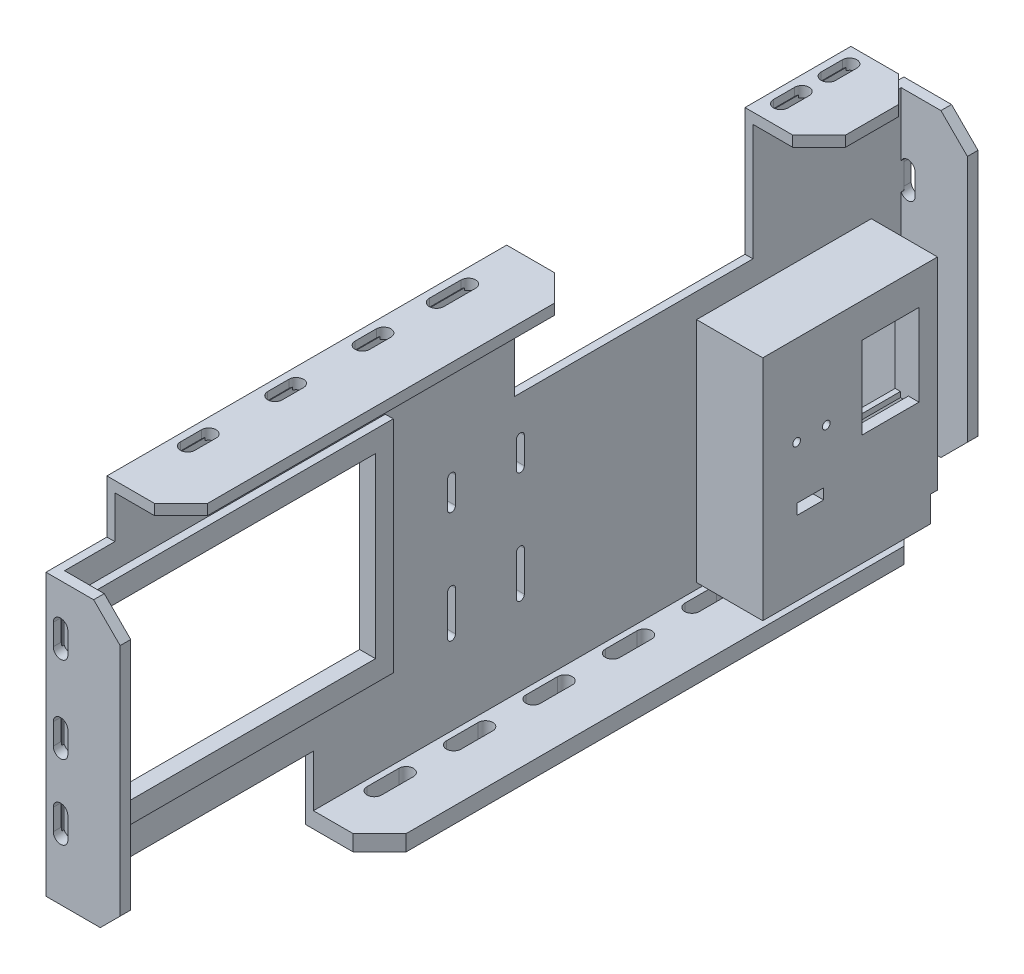
SolidWorks part; units mm, degrees
ref_plane "前视基准面" through (0, 0, 0) normal (0, 0, 1) x (1, 0, 0)
ref_plane "上视基准面" through (0, 0, 0) normal (0, 1, 0) x (1, 0, 0)
ref_plane "右视基准面" through (0, 0, 0) normal (1, 0, 0) x (0, 0, -1)
other "Configuration Table"
sketch "草图1" plane through (0, 0, 0) normal (1, 0, 0) x (0, 0, -1)
  line L0 (10, 87) -> (70, 87)
  line L1 (0, 0) -> (80, 0)
  line L2 (0, 0) -> (0, 97)
  line L3 (0, 97) -> (80, 97)
  line L4 (80, 0) -> (80, 97)
  line L5 (70, 10) -> (70, 87)
  line L6 (10, 10) -> (70, 10)
  line L7 (10, 10) -> (10, 87)
  dimension "D1" = 97
  dimension "D2" = 80
  dimension "D3" = 10
extrude "凸台-拉伸1" add sketch "草图1" along normal blind 6
sketch "草图2" plane through (6, 0, 0) normal (1, 0, 0) x (0, 0, -1)
  line L0 (80, 97) -> (0, 97) construction
  line L1 (10, 87) -> (70, 87)
  line L2 (10, 87) -> (10, 97)
  line L3 (10, 97) -> (70, 97)
  line L4 (70, 87) -> (70, 97)
  line L5 (0, 0) -> (80, 0) construction
  line L6 (10, 10) -> (70, 10)
  line L7 (10, 10) -> (10, 0)
  line L8 (10, 0) -> (70, 0)
  line L9 (70, 10) -> (70, 0)
extrude "凸台-拉伸2" add sketch "草图2" along normal blind 25
sketch "草图3" plane through (31, 0, 0) normal (1, 0, 0) x (0, 0, -1)
  line L1 (10, 87) -> (70, 87)
  line L2 (10, 87) -> (10, 10)
  line L3 (10, 10) -> (70, 10)
  line L4 (70, 87) -> (70, 10)
extrude "凸台-拉伸3" add sketch "草图3" against normal blind 4
sketch "草图4" plane through (27, 0, 0) normal (-1, 0, 0) x (0, 0, 1)
  line L0 (-70, 10) -> (-70, 87) construction
  line L1 (-66, 46) -> (-44.5, 46)
  line L2 (-66, 46) -> (-66, 77)
  line L3 (-66, 77) -> (-44.5, 77)
  line L4 (-44.5, 46) -> (-44.5, 77)
  line L5 (-70, 87) -> (-10, 87) construction
  dimension "D1" = 4
  dimension "D2" = 21.5
  dimension "D3" = 31
  dimension "D4" = 10
extrude "切除-拉伸1" cut sketch "草图4" against normal blind 4
sketch "草图5" plane through (27, 0, 0) normal (-1, 0, 0) x (0, 0, 1)
  line L0 (-66, 46) -> (-44.5, 46) construction
  line L1 (-44.5, 46) -> (-44.5, 77) construction
  line L2 (-66, 77) -> (-66, 46) construction
  line L3 (-44.5, 77) -> (-66, 77) construction
  line L4 (-66, 46) -> (-44.5, 46)
  line L5 (-44.5, 46) -> (-44.5, 77)
  line L6 (-66, 77) -> (-66, 46)
  line L7 (-44.5, 77) -> (-66, 77)
  line L8 (-68, 44) -> (-42.5, 44)
  line L9 (-42.5, 44) -> (-42.5, 79)
  line L10 (-42.5, 79) -> (-68, 79)
  line L11 (-68, 79) -> (-68, 44)
  dimension "D1" = 2
extrude "凸台-拉伸4" add sketch "草图5" along normal blind 5
sketch "草图6" plane through (0, 44, 0) normal (0, -1, 0) x (1, 0, 0)
  line L0 (22, -68) -> (27, -68) construction
  line L1 (24, -44.5) -> (27, -44.5)
  line L2 (24, -44.5) -> (24, -66)
  line L3 (24, -66) -> (27, -66)
  line L4 (27, -44.5) -> (27, -66)
  line L5 (22, -42.5) -> (27, -42.5) construction
  line L6 (22, -68) -> (22, -42.5) construction
  dimension "D1" = 2
  dimension "D2" = 2
  dimension "D3" = 2
  dimension "D4" = 3
extrude "切除-拉伸2" cut sketch "草图6" against normal blind 37
sketch "草图7" plane through (27, 0, 0) normal (-1, 0, 0) x (0, 0, 1)
  line L0 (-42.5, 44) -> (-42.5, 79) construction
  line L1 (-34.5, 44) -> (-16.3, 44)
  line L2 (-34.5, 44) -> (-34.5, 74.1)
  line L3 (-34.5, 74.1) -> (-16.3, 74.1)
  line L4 (-16.3, 44) -> (-16.3, 74.1)
  dimension "D1" = 18.2
  dimension "D2" = 30.1
  dimension "D3" = 8
  dimension "D4" = 44
extrude "切除-拉伸3" cut sketch "草图7" against normal blind 1.5
sketch "草图8" plane through (28.5, 0, 0) normal (-1, 0, 0) x (0, 0, 1)
  line L0 (-34.5, 44) -> (-16.3, 44) construction
  line L1 (-34.5, 44) -> (-16.3, 44) construction
  line L2 (-34.5, 74.1) -> (-34.5, 44) construction
  line L3 (-16.3, 44) -> (-16.3, 74.1) construction
  circle A0 centre (-31, 56) radius 1.45
  circle A1 centre (-19.8, 56) radius 1.45
  dimension "D1" = 12
  dimension "D3" = 2.9
  dimension "D4" = 2.9
  dimension "D2" = 12
  dimension "D5" = 3.5
  dimension "D6" = 3.5
extrude "切除-拉伸5" cut sketch "草图8" against normal blind 4.5
fillet "圆角1" radius 3 1 edges at (0, 0, -40)
fillet "圆角2" radius 3 1 edges at (0, 97, -40)
sketch "草图9" plane through (0, 97, 0) normal (0, 1, 0) x (1, 0, 0)
  line L0 (0, 0) -> (0, 80) construction
  line L1 (31, 70) -> (6, 70) construction
  circle A0 centre (6.2, 54) radius 2.75
  circle A1 centre (6.2, 46) radius 2.75
  circle A2 centre (6.2, 36) radius 2.75
  circle A3 centre (6.2, 28) radius 2.75
  dimension "D1" = 6.2
  dimension "D3" = 5.5
  dimension "D2" = 16
  dimension "D4" = 8
  dimension "D5" = 10
  dimension "D6" = 8
extrude "切除-拉伸6" cut sketch "草图9" against normal blind 10
sketch "草图10" plane through (0, 0, 0) normal (-1, 0, 0) x (0, 0, 1)
  line L1 (-70, 87) -> (-10, 87)
  line L2 (-70, 87) -> (-70, 92)
  line L3 (-70, 92) -> (-10, 92)
  line L4 (-10, 87) -> (-10, 92)
  dimension "D1" = 5
extrude "切除-拉伸7" cut sketch "草图10" against normal blind 20
sketch "草图11" plane through (0, 0, 0) normal (-1, 0, 0) x (0, 0, 1)
  line L0 (-10, 92) -> (-10, 10) construction
  line L1 (-70, 10) -> (-10, 10)
  line L2 (-70, 10) -> (-70, 20)
  line L3 (-70, 20) -> (-10, 20)
  line L4 (-10, 10) -> (-10, 20)
  dimension "D1" = 10
extrude "凸台-拉伸5" add sketch "草图11" against normal blind 5
sketch "草图12" plane through (0, 0, 0) normal (-1, 0, 0) x (0, 0, 1)
  line L0 (0, 0) -> (-80, 0) construction
  line L1 (0, 94) -> (0, 3) construction
  circle A0 centre (-61, 14) radius 2.7
  circle A1 centre (-46, 14) radius 2.7
  circle A2 centre (-30, 14) radius 2.7
  circle A3 centre (-15, 14) radius 2.7
  dimension "D1" = 14
  dimension "D2" = 5.4
  dimension "D4" = 5.4
  dimension "D5" = 5.4
  dimension "D6" = 5.4
  dimension "D3" = 15
  dimension "D7" = 15
  dimension "D8" = 15
  dimension "D9" = 16
extrude "切除-拉伸8" cut sketch "草图12" against normal blind 5
sketch "草图13" plane through (0, 0, -70) normal (0, 0, -1) x (-1, 0, 0)
  line L1 (-6, 10) -> (-27, 10)
  line L2 (-6, 10) -> (-6, 7)
  line L3 (-6, 7) -> (-27, 7)
  line L4 (-27, 10) -> (-27, 7)
  dimension "D1" = 3
extrude "切除-拉伸9" cut sketch "草图13" against normal blind 80
sketch "草图14" plane through (0, 0, 0) normal (-1, 0, 0) x (0, 0, 1)
  line L1 (-121.2338, 126.064) -> (53.7432, 126.064)
  line L2 (-121.2338, 126.064) -> (-121.2338, -60.5781)
  line L3 (-121.2338, -60.5781) -> (53.7432, -60.5781)
  line L4 (53.7432, 126.064) -> (53.7432, -60.5781)
extrude "切除-拉伸11" cut sketch "草图14" against normal blind 22
sketch "草图15" plane through (22, 0, 0) normal (-1, 0, 0) x (0, 0, 1)
  line L4 (-10, 87) -> (-10, 97)
  line L5 (-10, 97) -> (-70, 97)
  line L6 (-70, 97) -> (-70, 87)
  line L7 (-70, 87) -> (-10, 87)
  line L8 (-10, 87) -> (-10, 97)
  line L9 (-10, 97) -> (-70, 97)
  line L10 (-70, 97) -> (-70, 87)
  line L11 (-70, 87) -> (-10, 87)
  line L12 (-70, 0) -> (-10, 0)
  line L13 (-10, 0) -> (-10, 7)
  line L14 (-10, 7) -> (-70, 7)
  line L15 (-70, 7) -> (-70, 0)
  line L16 (-70, 0) -> (-10, 0)
  line L17 (-10, 0) -> (-10, 7)
  line L18 (-10, 7) -> (-70, 7)
  line L19 (-70, 7) -> (-70, 0)
  dimension "D1" = 0
  dimension "D2" = 0
extrude "切除-拉伸12" cut sketch "草图15" against normal blind 22
sketch "草图19" plane through (31, 0, 0) normal (1, 0, 0) x (0, 0, -1)
  line L0 (86.2882, 145.23) -> (-233.7118, 145.23)
  line L1 (90.2882, -6.27) -> (-237.7118, -6.27)
  line L2 (90.2882, -6.27) -> (90.2882, 149.23)
  line L3 (90.2882, 149.23) -> (-237.7118, 149.23)
  line L4 (-237.7118, -6.27) -> (-237.7118, 149.23)
  line L5 (-233.7118, -2.27) -> (-233.7118, 145.23)
  line L6 (86.2882, -2.27) -> (-233.7118, -2.27)
  line L7 (86.2882, -2.27) -> (86.2882, 145.23)
  dimension "D1" = 155.5
  dimension "D2" = 328
  dimension "D3" = 4
extrude "凸台-拉伸6" add sketch "草图19" against normal blind 28 separate body
sketch "草图20" plane through (31, 0, 0) normal (1, 0, 0) x (0, 0, -1)
  line L0 (73, 90) -> (7, 90)
  line L1 (7, 90) -> (7, 4)
  line L2 (7, 4) -> (73, 4)
  line L3 (73, 4) -> (73, 90)
  line L4 (70, 7) -> (70, 87)
  line L5 (70, 87) -> (10, 87)
  line L6 (10, 87) -> (10, 7)
  line L7 (10, 7) -> (70, 7)
  line L8 (70, 7) -> (70, 87)
  line L9 (70, 87) -> (10, 87)
  line L10 (10, 87) -> (10, 7)
  line L11 (10, 7) -> (70, 7)
  dimension "D1" = 0
  dimension "D2" = 3
extrude "凸台-拉伸7" add sketch "草图20" against normal blind 28
sketch "草图21" plane through (3, 0, 0) normal (-1, 0, 0) x (0, 0, 1)
  line L4 (-90.2882, 149.23) -> (-90.2882, -6.27)
  line L5 (-90.2882, -6.27) -> (237.7118, -6.27)
  line L6 (237.7118, -6.27) -> (237.7118, 149.23)
  line L7 (237.7118, 149.23) -> (-90.2882, 149.23)
  line L8 (-90.2882, 149.23) -> (-90.2882, -6.27)
  line L9 (-90.2882, -6.27) -> (237.7118, -6.27)
  line L10 (237.7118, -6.27) -> (237.7118, 149.23)
  line L11 (237.7118, 149.23) -> (-90.2882, 149.23)
  line L12 (-73, 90) -> (-73, 4)
  line L13 (-73, 4) -> (-7, 4)
  line L14 (-7, 4) -> (-7, 90)
  line L15 (-7, 90) -> (-73, 90)
  line L16 (-73, 90) -> (-73, 4)
  line L17 (-73, 4) -> (-7, 4)
  line L18 (-7, 4) -> (-7, 90)
  line L19 (-7, 90) -> (-73, 90)
  dimension "D1" = 0
  dimension "D2" = 0
extrude "凸台-拉伸8" add sketch "草图21" against normal blind 3
sketch "草图22" plane through (6, 0, 0) normal (1, 0, 0) x (0, 0, -1)
  line L0 (-85.5598, 84.73) -> (-85.5598, 74.73) construction
  line L1 (-82.5598, 84.73) -> (-82.5598, 74.73)
  line L2 (-88.5598, 84.73) -> (-88.5598, 74.73)
  line L3 (-85.5598, 32.73) -> (-85.5598, 47.73) construction
  line L4 (-88.5598, 32.73) -> (-88.5598, 47.73)
  line L5 (-82.5598, 32.73) -> (-82.5598, 47.73)
  line L6 (-59.5598, 74.7258) -> (-59.5598, 84.7258) construction
  line L7 (-62.5598, 74.7258) -> (-62.5598, 84.7258)
  line L8 (-56.5598, 74.7258) -> (-56.5598, 84.7258)
  line L9 (-59.5598, 32.73) -> (-59.5598, 47.73) construction
  line L10 (-62.5598, 32.73) -> (-62.5598, 47.73)
  line L11 (-56.5598, 32.73) -> (-56.5598, 47.73)
  line L12 (-233.7118, -2.27) -> (86.2882, -2.27) construction
  arc A0 (-82.5598, 84.73) -> (-88.5598, 84.73) centre (-85.5598, 84.73) ccw
  arc A1 (-88.5598, 74.73) -> (-82.5598, 74.73) centre (-85.5598, 74.73) ccw
  arc A2 (-88.5598, 32.73) -> (-82.5598, 32.73) centre (-85.5598, 32.73) ccw
  arc A3 (-82.5598, 47.73) -> (-88.5598, 47.73) centre (-85.5598, 47.73) ccw
  arc A4 (-62.5598, 74.7258) -> (-56.5598, 74.7258) centre (-59.5598, 74.7258) ccw
  arc A5 (-56.5598, 84.7258) -> (-62.5598, 84.7258) centre (-59.5598, 84.7258) ccw
  arc A6 (-62.5598, 32.73) -> (-56.5598, 32.73) centre (-59.5598, 32.73) ccw
  arc A7 (-56.5598, 47.73) -> (-62.5598, 47.73) centre (-59.5598, 47.73) ccw
  point P2 (-85.5598, 79.73)
  point P7 (-85.5598, 40.23)
  point P14 (-59.5598, 79.7258)
  point P21 (-59.5598, 40.23)
  dimension "D4" = 52
  dimension "D7" = 3
  dimension "D8" = 3
  dimension "D9" = 3
  dimension "D10" = 3
  dimension "D1" = 26
  dimension "D2" = 10
  dimension "D3" = 10
  dimension "D5" = 15
  dimension "D6" = 15
  dimension "D11" = 35
extrude "切除-拉伸13" cut sketch "草图22" against normal blind 3
sketch "草图24" plane through (6, 0, 0) normal (1, 0, 0) x (0, 0, -1)
  line L0 (-88.5598, 47.73) -> (-88.5598, 32.73) construction
  line L1 (-118.5598, 42.73) -> (-223.8598, 42.73)
  line L2 (-118.5598, 42.73) -> (-118.5598, 109.83)
  line L3 (-118.5598, 109.83) -> (-223.8598, 109.83)
  line L4 (-223.8598, 42.73) -> (-223.8598, 109.83)
  line L5 (-233.7118, -2.27) -> (86.2882, -2.27) construction
  dimension "D1" = 105.3
  dimension "D2" = 67.1
  dimension "D3" = 30
  dimension "D4" = 45
extrude "切除-拉伸15" cut sketch "草图24" against normal blind 3
sketch "草图26" plane through (6, 0, 0) normal (1, 0, 0) x (0, 0, -1)
  line L0 (-118.5598, 42.73) -> (-118.5598, 109.83) construction
  line L1 (-118.5598, 42.73) -> (-118.5598, 109.83)
  line L3 (-118.5598, 109.83) -> (-223.8598, 109.83) construction
  line L4 (-233.7118, -2.27) -> (86.2882, -2.27)
  line L5 (86.2882, -2.27) -> (86.2882, 145.23)
  line L6 (86.2882, 145.23) -> (-233.7118, 145.23)
  line L7 (-233.7118, 145.23) -> (-233.7118, -2.27)
  line L8 (-233.7118, -2.27) -> (86.2882, -2.27)
  line L9 (86.2882, -2.27) -> (86.2882, 145.23)
  line L10 (86.2882, 145.23) -> (-233.7118, 145.23)
  line L11 (-233.7118, 145.23) -> (-233.7118, -2.27)
  line L12 (-118.5598, 109.83) -> (-223.8598, 109.83)
  line L13 (-223.8598, 42.73) -> (-118.5598, 42.73) construction
  line L14 (-223.8598, 109.83) -> (-223.8598, 42.73) construction
  line L15 (-223.8598, 42.73) -> (-118.5598, 42.73)
  line L16 (-223.8598, 109.83) -> (-223.8598, 42.73)
  line L17 (-110.5598, 117.83) -> (-231.8598, 117.83)
  line L18 (-231.8598, 117.83) -> (-231.8598, 34.73)
  line L19 (-231.8598, 34.73) -> (-110.5598, 34.73)
  line L20 (-110.5598, 34.73) -> (-110.5598, 117.83)
  line M7 (-223.8598, 109.83) -> (-118.5598, 109.83)
  line M8 (-118.5598, 109.83) -> (-118.5598, 42.73)
  line M9 (-118.5598, 42.73) -> (-223.8598, 42.73)
  line M10 (-223.8598, 42.73) -> (-223.8598, 109.83)
  dimension "D1" = 0
  dimension "D2" = 8
extrude "凸台-拉伸11" add sketch "草图26" along normal blind 3 contours L19 L20 L17 L18 M10 M7 M8 M9 region at (6, 76.28, 112.0302)
sketch "草图27" plane through (31, 0, 0) normal (1, 0, 0) x (0, 0, -1)
  line L1 (-237.7118, -6.27) -> (-137.7118, -6.27)
  line L2 (-237.7118, -6.27) -> (-237.7118, 18.73)
  line L3 (-237.7118, 18.73) -> (-137.7118, 18.73)
  line L4 (-137.7118, -6.27) -> (-137.7118, 18.73)
  dimension "D1" = 25
  dimension "D2" = 100
extrude "切除-拉伸16" cut sketch "草图27" against normal blind 36
sketch "草图28" plane through (31, 0, 0) normal (1, 0, 0) x (0, 0, -1)
  line L1 (90.2882, -6.27) -> (70.2882, -6.27)
  line L2 (90.2882, -6.27) -> (90.2882, 13.73)
  line L3 (90.2882, 13.73) -> (70.2882, 13.73)
  line L4 (70.2882, -6.27) -> (70.2882, 13.73)
  dimension "D1" = 20
  dimension "D2" = 20
extrude "切除-拉伸17" cut sketch "草图28" against normal blind 36
sketch "草图29" plane through (31, 0, 0) normal (1, 0, 0) x (0, 0, -1)
  line L1 (90.2882, 149.23) -> (68.2882, 149.23)
  line L2 (90.2882, 149.23) -> (90.2882, 127.23)
  line L3 (90.2882, 127.23) -> (68.2882, 127.23)
  line L4 (68.2882, 149.23) -> (68.2882, 127.23)
  line L5 (-237.7118, 149.23) -> (-212.7118, 149.23)
  line L6 (-237.7118, 149.23) -> (-237.7118, 127.23)
  line L7 (-237.7118, 127.23) -> (-212.7118, 127.23)
  line L8 (-212.7118, 149.23) -> (-212.7118, 127.23)
  dimension "D1" = 22
  dimension "D2" = 22
  dimension "D3" = 25
  dimension "D4" = 22
extrude "切除-拉伸18" cut sketch "草图29" against normal blind 36
sketch "草图31" plane through (31, 0, 0) normal (1, 0, 0) x (0, 0, -1)
  line L0 (68.2882, 149.23) -> (-212.7118, 149.23) construction
  line L1 (28.2882, 149.23) -> (-61.7118, 149.23)
  line L2 (28.2882, 149.23) -> (28.2882, 99.23)
  line L3 (28.2882, 99.23) -> (-61.7118, 99.23)
  line L4 (-61.7118, 149.23) -> (-61.7118, 99.23)
  line L5 (90.2882, 13.73) -> (90.2882, 127.23) construction
  dimension "D1" = 62
  dimension "D2" = 90
  dimension "D3" = 50
extrude "切除-拉伸19" cut sketch "草图31" against normal blind 36
sketch "草图32" plane through (27, 0, 0) normal (-1, 0, 0) x (0, 0, 1)
  line L0 (-34.5, 44) -> (-16.3, 44) construction
  line L1 (-30, 36) -> (-20, 36)
  line L2 (-30, 36) -> (-30, 32)
  line L3 (-30, 32) -> (-20, 32)
  line L4 (-20, 36) -> (-20, 32)
  line L5 (-10, 87) -> (-10, 7) construction
  dimension "D1" = 8
  dimension "D2" = 4
  dimension "D3" = 10
  dimension "D4" = 10
extrude "切除-拉伸20" cut sketch "草图32" against normal blind 36
sketch "草图33" plane through (0, 149.23, 0) normal (0, 1, 0) x (1, 0, 0)
  line L0 (8.5, 62.2882) -> (8.5, 54.2882) construction
  line L3 (11.25, 62.2882) -> (11.25, 54.2882)
  line L6 (8.5, -81.7118) -> (8.5, -93.7118) construction
  line L7 (11.25, -81.7118) -> (11.25, -93.7118)
  line L8 (5.75, -81.7118) -> (5.75, -93.7118)
  line L9 (8.5, -113.7118) -> (8.5, -121.7118) construction
  line L10 (11.25, -113.7118) -> (11.25, -121.7118)
  line L11 (5.75, -113.7118) -> (5.75, -121.7118)
  line L12 (8.5, -146.7118) -> (8.5, -154.7118) construction
  line L13 (11.25, -146.7118) -> (11.25, -154.7118)
  line L14 (5.75, -146.7118) -> (5.75, -154.7118)
  line L15 (8.5, -179.7118) -> (8.5, -187.7118) construction
  line L16 (11.25, -179.7118) -> (11.25, -187.7118)
  line L17 (5.75, -179.7118) -> (5.75, -187.7118)
  line L18 (3, -61.7118) -> (3, -212.7118) construction
  line L19 (3, -212.7118) -> (31, -212.7118) construction
  line L20 (5.75, 62.2882) -> (5.75, 54.2882)
  line L22 (8.5, 44.2882) -> (8.5, 36.2882) construction
  line L23 (11.25, 44.2882) -> (11.25, 36.2882)
  line L24 (5.75, 44.2882) -> (5.75, 36.2882)
  line L25 (3, 68.2882) -> (3, 28.2882) construction
  line L26 (3, 68.2882) -> (31, 68.2882) construction
  line L27 (3, 28.2882) -> (31, 28.2882) construction
  arc A4 (11.25, -81.7118) -> (5.75, -81.7118) centre (8.5, -81.7118) ccw
  arc A5 (5.75, -93.7118) -> (11.25, -93.7118) centre (8.5, -93.7118) ccw
  arc A6 (11.25, -113.7118) -> (5.75, -113.7118) centre (8.5, -113.7118) ccw
  arc A7 (5.75, -121.7118) -> (11.25, -121.7118) centre (8.5, -121.7118) ccw
  arc A8 (11.25, -146.7118) -> (5.75, -146.7118) centre (8.5, -146.7118) ccw
  arc A9 (5.75, -154.7118) -> (11.25, -154.7118) centre (8.5, -154.7118) ccw
  arc A10 (11.25, -179.7118) -> (5.75, -179.7118) centre (8.5, -179.7118) ccw
  arc A11 (5.75, -187.7118) -> (11.25, -187.7118) centre (8.5, -187.7118) ccw
  arc A12 (11.25, 62.2882) -> (5.75, 62.2882) centre (8.5, 62.2882) ccw
  arc A13 (5.75, 54.2882) -> (11.25, 54.2882) centre (8.5, 54.2882) ccw
  arc A14 (11.25, 44.2882) -> (5.75, 44.2882) centre (8.5, 44.2882) ccw
  arc A15 (5.75, 36.2882) -> (11.25, 36.2882) centre (8.5, 36.2882) ccw
  point P2 (5.75, 58.3197)
  point P3 (8.5, 58.2882)
  point P7 (5.75, 37.9476)
  point P9 (8.5, 40.2882)
  point P14 (8.5, -87.7118)
  point P21 (8.5, -117.7118)
  point P28 (8.5, -150.7118)
  point P35 (8.5, -183.7118)
  dimension "D9" = 25
  dimension "D1" = 5.5
  dimension "D2" = 5.5
  dimension "D3" = 8
  dimension "D4" = 25
  dimension "D5" = 25
  dimension "D6" = 8
  dimension "D7" = 5.5
  dimension "D8" = 8
  dimension "D10" = 12
  dimension "D11" = 20
  dimension "D12" = 5.5
  dimension "D13" = 5.5
  dimension "D14" = 8
  dimension "D15" = 6
  dimension "D16" = 8
  dimension "D17" = 8
extrude "切除-拉伸21" cut sketch "草图33" against normal blind 5
sketch "草图34" plane through (0, 0, -90.2882) normal (0, 0, -1) x (-1, 0, 0)
  line L0 (-8.5, 102.23) -> (-8.5, 94.23) construction
  line L1 (-5.75, 102.23) -> (-5.75, 94.23)
  line L2 (-11.25, 102.23) -> (-11.25, 94.23)
  line L3 (-8.5, 64.73) -> (-8.5, 56.73) construction
  line L4 (-5.75, 64.73) -> (-5.75, 56.73)
  line L5 (-11.25, 64.73) -> (-11.25, 56.73)
  line L6 (-8.5, 31.73) -> (-8.5, 23.73) construction
  line L7 (-5.75, 31.73) -> (-5.75, 23.73)
  line L8 (-11.25, 31.73) -> (-11.25, 23.73)
  line L9 (-3, 13.73) -> (-3, 127.23) construction
  line L10 (-3, 13.73) -> (-31, 13.73) construction
  line L11 (-3, 127.23) -> (-31, 127.23) construction
  arc A0 (-5.75, 102.23) -> (-11.25, 102.23) centre (-8.5, 102.23) ccw
  arc A1 (-11.25, 94.23) -> (-5.75, 94.23) centre (-8.5, 94.23) ccw
  arc A2 (-5.75, 64.73) -> (-11.25, 64.73) centre (-8.5, 64.73) ccw
  arc A3 (-11.25, 56.73) -> (-5.75, 56.73) centre (-8.5, 56.73) ccw
  arc A4 (-5.75, 31.73) -> (-11.25, 31.73) centre (-8.5, 31.73) ccw
  arc A5 (-11.25, 23.73) -> (-5.75, 23.73) centre (-8.5, 23.73) ccw
  point P2 (-8.5, 98.23)
  point P7 (-8.5, 60.73)
  point P14 (-8.5, 27.73)
  dimension "D1" = 8
  dimension "D2" = 8
  dimension "D3" = 8
  dimension "D4" = 5.5
  dimension "D5" = 5.5
  dimension "D6" = 5.5
  dimension "D7" = 5.5
  dimension "D8" = 10
  dimension "D9" = 25
  dimension "D10" = 25
extrude "切除-拉伸22" cut sketch "草图34" against normal blind 5
sketch "草图35" plane through (0, 0, 237.7118) normal (0, 0, 1) x (1, 0, 0)
  line L0 (8.5, 112.23) -> (8.5, 104.23) construction
  line L1 (11.25, 112.23) -> (11.25, 104.23)
  line L2 (5.75, 112.23) -> (5.75, 104.23)
  line L3 (8.5, 79.73) -> (8.5, 71.73) construction
  line L4 (11.25, 79.73) -> (11.25, 71.73)
  line L5 (5.75, 79.73) -> (5.75, 71.73)
  line L6 (8.5, 51.73) -> (8.5, 43.73) construction
  line L7 (11.25, 51.73) -> (11.25, 43.73)
  line L8 (5.75, 51.73) -> (5.75, 43.73)
  line L9 (3, 127.23) -> (3, 18.73) construction
  line L10 (3, 18.73) -> (31, 18.73) construction
  line L11 (3, 127.23) -> (31, 127.23) construction
  arc A0 (11.25, 112.23) -> (5.75, 112.23) centre (8.5, 112.23) ccw
  arc A1 (5.75, 104.23) -> (11.25, 104.23) centre (8.5, 104.23) ccw
  arc A2 (11.25, 79.73) -> (5.75, 79.73) centre (8.5, 79.73) ccw
  arc A3 (5.75, 71.73) -> (11.25, 71.73) centre (8.5, 71.73) ccw
  arc A4 (11.25, 51.73) -> (5.75, 51.73) centre (8.5, 51.73) ccw
  arc A5 (5.75, 43.73) -> (11.25, 43.73) centre (8.5, 43.73) ccw
  point P2 (8.5, 108.23)
  point P7 (8.5, 75.73)
  point P14 (8.5, 47.73)
  dimension "D1" = 8
  dimension "D2" = 8
  dimension "D3" = 8
  dimension "D4" = 5.5
  dimension "D5" = 5.5
  dimension "D6" = 5.5
  dimension "D7" = 5.5
  dimension "D8" = 25
  dimension "D9" = 20
  dimension "D10" = 15
extrude "切除-拉伸23" cut sketch "草图35" against normal blind 5
sketch "草图36" plane through (0, -6.27, 0) normal (0, -1, 0) x (1, 0, 0)
  line L0 (11, 119.7118) -> (11, 107.7118) construction
  line L1 (13.75, 119.7118) -> (13.75, 107.7118)
  line L2 (8.25, 119.7118) -> (8.25, 107.7118)
  line L3 (3, 137.7118) -> (3, -70.2882) construction
  line L4 (3, 137.7118) -> (31, 137.7118) construction
  line L5 (11, 89.7118) -> (11, 77.7118) construction
  line L6 (13.75, 89.7118) -> (13.75, 77.7118)
  line L7 (8.25, 89.7118) -> (8.25, 77.7118)
  line L8 (11, 59.7118) -> (11, 47.7118) construction
  line L9 (13.75, 59.7118) -> (13.75, 47.7118)
  line L10 (8.25, 59.7118) -> (8.25, 47.7118)
  line L11 (11, 29.7118) -> (11, 17.7118) construction
  line L12 (13.75, 29.7118) -> (13.75, 17.7118)
  line L13 (8.25, 29.7118) -> (8.25, 17.7118)
  line L14 (11, -0.2882) -> (11, -12.2882) construction
  line L15 (13.75, -0.2882) -> (13.75, -12.2882)
  line L16 (8.25, -0.2882) -> (8.25, -12.2882)
  line L17 (11, -30.2882) -> (11, -42.2882) construction
  line L18 (13.75, -30.2882) -> (13.75, -42.2882)
  line L19 (8.25, -30.2882) -> (8.25, -42.2882)
  arc A0 (13.75, 119.7118) -> (8.25, 119.7118) centre (11, 119.7118) ccw
  arc A1 (8.25, 107.7118) -> (13.75, 107.7118) centre (11, 107.7118) ccw
  arc A2 (13.75, 89.7118) -> (8.25, 89.7118) centre (11, 89.7118) ccw
  arc A3 (8.25, 77.7118) -> (13.75, 77.7118) centre (11, 77.7118) ccw
  arc A4 (13.75, 59.7118) -> (8.25, 59.7118) centre (11, 59.7118) ccw
  arc A5 (8.25, 47.7118) -> (13.75, 47.7118) centre (11, 47.7118) ccw
  arc A6 (13.75, 29.7118) -> (8.25, 29.7118) centre (11, 29.7118) ccw
  arc A7 (8.25, 17.7118) -> (13.75, 17.7118) centre (11, 17.7118) ccw
  arc A8 (13.75, -0.2882) -> (8.25, -0.2882) centre (11, -0.2882) ccw
  arc A9 (8.25, -12.2882) -> (13.75, -12.2882) centre (11, -12.2882) ccw
  arc A10 (13.75, -30.2882) -> (8.25, -30.2882) centre (11, -30.2882) ccw
  arc A11 (8.25, -42.2882) -> (13.75, -42.2882) centre (11, -42.2882) ccw
  point P2 (11, 113.7118)
  point P15 (11, 83.7118)
  point P22 (11, 53.7118)
  point P29 (11, 23.7118)
  point P36 (11, -6.2882)
  point P43 (11, -36.2882)
  dimension "D1" = 8
  dimension "D2" = 5.5
  dimension "D3" = 30
  dimension "D4" = 12
  dimension "D5" = 6
extrude "切除-拉伸24" cut sketch "草图36" against normal blind 5
chamfer "倒角1" distance 10 angle 45 10 edges at (31, -4.27, 137.7118) (31, -4.27, -70.2882) (31, 13.73, -88.2882) (31, 127.23, -88.2882) (31, 147.23, -28.2882) (31, 147.23, -68.2882) (31, 147.23, 61.7118) (31, 147.23, 212.7118) (31, 127.23, 235.7118) (31, 18.73, 235.7118)
sketch "草图37" plane through (31, 0, 0) normal (1, 0, 0) x (0, 0, -1)
  line L0 (70.2882, -2.27) -> (70.2882, -6.27) construction
  line L1 (-137.7118, -6.27) -> (70.2882, -6.27)
  line L2 (-137.7118, -6.27) -> (-137.7118, -4.27)
  line L3 (-137.7118, -4.27) -> (70.2882, -4.27)
  line L4 (70.2882, -6.27) -> (70.2882, -4.27)
extrude "切除-拉伸25" cut sketch "草图37" against normal blind 32
sketch "草图38" plane through (0, -2.27, 0) normal (0, 1, 0) x (1, 0, 0)
  line L0 (8.25, -119.7118) -> (8.25, -107.7118) construction
  line L1 (13.75, -107.7118) -> (13.75, -119.7118) construction
  line L2 (13.75, -77.7118) -> (13.75, -89.7118) construction
  line L3 (8.25, -89.7118) -> (8.25, -77.7118) construction
  line L4 (8.25, -59.7118) -> (8.25, -47.7118) construction
  line L5 (13.75, -47.7118) -> (13.75, -59.7118) construction
  line L6 (6, -137.7118) -> (21, -137.7118)
  line L7 (21, -137.7118) -> (31, -127.7118)
  line L8 (31, -127.7118) -> (31, 60.2882)
  line L9 (31, 60.2882) -> (21, 70.2882)
  line L10 (21, 70.2882) -> (6, 70.2882)
  line L11 (6, 70.2882) -> (6, -137.7118)
  line L12 (6, -137.7118) -> (21, -137.7118)
  line L13 (21, -137.7118) -> (31, -127.7118)
  line L14 (31, -127.7118) -> (31, 60.2882)
  line L15 (31, 60.2882) -> (21, 70.2882)
  line L16 (21, 70.2882) -> (6, 70.2882)
  line L17 (6, 70.2882) -> (6, -137.7118)
  line L18 (8.25, -29.7118) -> (8.25, -17.7118) construction
  line L19 (13.75, -17.7118) -> (13.75, -29.7118) construction
  line L20 (13.75, 12.2882) -> (13.75, 0.2882) construction
  line L21 (8.25, 0.2882) -> (8.25, 12.2882) construction
  line L22 (8.25, 30.2882) -> (8.25, 42.2882) construction
  line L23 (13.75, 42.2882) -> (13.75, 30.2882) construction
  line L24 (8.25, -119.7118) -> (8.25, -107.7118)
  line L25 (13.75, -107.7118) -> (13.75, -119.7118)
  line L26 (13.75, -77.7118) -> (13.75, -89.7118)
  line L27 (8.25, -89.7118) -> (8.25, -77.7118)
  line L28 (8.25, -59.7118) -> (8.25, -47.7118)
  line L29 (13.75, -47.7118) -> (13.75, -59.7118)
  line L30 (8.25, -29.7118) -> (8.25, -17.7118)
  line L31 (13.75, -17.7118) -> (13.75, -29.7118)
  line L32 (13.75, 12.2882) -> (13.75, 0.2882)
  line L33 (8.25, 0.2882) -> (8.25, 12.2882)
  line L34 (8.25, 30.2882) -> (8.25, 42.2882)
  line L35 (13.75, 42.2882) -> (13.75, 30.2882)
  arc A0 (8.25, -119.7118) -> (13.75, -119.7118) centre (11, -119.7118) ccw construction
  arc A1 (13.75, -107.7118) -> (8.25, -107.7118) centre (11, -107.7118) ccw construction
  arc A2 (8.25, -89.7118) -> (13.75, -89.7118) centre (11, -89.7118) ccw construction
  arc A3 (13.75, -77.7118) -> (8.25, -77.7118) centre (11, -77.7118) ccw construction
  arc A4 (8.25, -59.7118) -> (13.75, -59.7118) centre (11, -59.7118) ccw construction
  arc A5 (13.75, -47.7118) -> (8.25, -47.7118) centre (11, -47.7118) ccw construction
  arc A6 (8.25, -29.7118) -> (13.75, -29.7118) centre (11, -29.7118) ccw construction
  arc A7 (13.75, -17.7118) -> (8.25, -17.7118) centre (11, -17.7118) ccw construction
  arc A8 (8.25, 0.2882) -> (13.75, 0.2882) centre (11, 0.2882) ccw construction
  arc A9 (13.75, 12.2882) -> (8.25, 12.2882) centre (11, 12.2882) ccw construction
  arc A10 (8.25, 30.2882) -> (13.75, 30.2882) centre (11, 30.2882) ccw construction
  arc A11 (13.75, 42.2882) -> (8.25, 42.2882) centre (11, 42.2882) ccw construction
  arc A12 (8.25, -119.7118) -> (13.75, -119.7118) centre (11, -119.7118) ccw
  arc A13 (13.75, -107.7118) -> (8.25, -107.7118) centre (11, -107.7118) ccw
  arc A14 (8.25, -89.7118) -> (13.75, -89.7118) centre (11, -89.7118) ccw
  arc A15 (13.75, -77.7118) -> (8.25, -77.7118) centre (11, -77.7118) ccw
  arc A16 (8.25, -59.7118) -> (13.75, -59.7118) centre (11, -59.7118) ccw
  arc A17 (13.75, -47.7118) -> (8.25, -47.7118) centre (11, -47.7118) ccw
  arc A18 (8.25, -29.7118) -> (13.75, -29.7118) centre (11, -29.7118) ccw
  arc A19 (13.75, -17.7118) -> (8.25, -17.7118) centre (11, -17.7118) ccw
  arc A20 (8.25, 0.2882) -> (13.75, 0.2882) centre (11, 0.2882) ccw
  arc A21 (13.75, 12.2882) -> (8.25, 12.2882) centre (11, 12.2882) ccw
  arc A22 (8.25, 30.2882) -> (13.75, 30.2882) centre (11, 30.2882) ccw
  arc A23 (13.75, 42.2882) -> (8.25, 42.2882) centre (11, 42.2882) ccw
  dimension "D1" = 0
extrude "凸台-拉伸12" add sketch "草图38" along normal blind 4
sketch "草图39" plane through (0, 149.23, 0) normal (0, 1, 0) x (1, 0, 0)
  line L0 (11.25, 36.2882) -> (11.25, 44.2882) construction
  line L1 (5.75, 44.2882) -> (5.75, 36.2882) construction
  line L2 (5.75, 62.2882) -> (5.75, 54.2882) construction
  line L3 (11.25, 54.2882) -> (11.25, 62.2882) construction
  line L4 (11.25, 36.2882) -> (11.25, 44.2882)
  line L5 (5.75, 44.2882) -> (5.75, 36.2882)
  line L6 (3, 28.2882) -> (21, 28.2882)
  line L7 (21, 28.2882) -> (31, 38.2882)
  line L8 (31, 38.2882) -> (31, 58.2882)
  line L9 (31, 58.2882) -> (21, 68.2882)
  line L10 (21, 68.2882) -> (3, 68.2882)
  line L11 (3, 68.2882) -> (3, 28.2882)
  line L12 (3, 28.2882) -> (21, 28.2882)
  line L13 (21, 28.2882) -> (31, 38.2882)
  line L14 (31, 38.2882) -> (31, 58.2882)
  line L15 (31, 58.2882) -> (21, 68.2882)
  line L16 (21, 68.2882) -> (3, 68.2882)
  line L17 (3, 68.2882) -> (3, 28.2882)
  line L18 (5.75, 62.2882) -> (5.75, 54.2882)
  line L19 (11.25, 54.2882) -> (11.25, 62.2882)
  line L20 (11.25, -187.7118) -> (11.25, -179.7118) construction
  line L21 (5.75, -179.7118) -> (5.75, -187.7118) construction
  line L22 (6, -122.8574) -> (6, -112.5662)
  line L23 (5.75, -113.7118) -> (5.75, -121.7118)
  line L24 (6, -122.8574) -> (6, -112.5662)
  line L25 (5.75, -113.7118) -> (5.75, -121.7118)
  line L26 (31, -202.7118) -> (31, -71.7118)
  line L27 (31, -71.7118) -> (21, -61.7118)
  line L28 (21, -61.7118) -> (3, -61.7118)
  line L29 (3, -61.7118) -> (3, -212.7118)
  line L30 (3, -212.7118) -> (21, -212.7118)
  line L31 (21, -212.7118) -> (31, -202.7118)
  line L32 (31, -202.7118) -> (31, -71.7118)
  line L33 (31, -71.7118) -> (21, -61.7118)
  line L34 (21, -61.7118) -> (3, -61.7118)
  line L35 (3, -61.7118) -> (3, -212.7118)
  line L36 (3, -212.7118) -> (21, -212.7118)
  line L37 (21, -212.7118) -> (31, -202.7118)
  line L38 (5.75, -146.7118) -> (5.75, -154.7118) construction
  line L39 (11.25, -154.7118) -> (11.25, -146.7118) construction
  line L40 (11.25, -121.7118) -> (11.25, -113.7118) construction
  line L41 (5.75, -81.7118) -> (5.75, -93.7118) construction
  line L42 (11.25, -93.7118) -> (11.25, -81.7118) construction
  line L43 (11.25, -187.7118) -> (11.25, -179.7118)
  line L44 (5.75, -179.7118) -> (5.75, -187.7118)
  line L45 (5.75, -146.7118) -> (5.75, -154.7118)
  line L46 (11.25, -154.7118) -> (11.25, -146.7118)
  line L47 (11.25, -121.7118) -> (11.25, -113.7118)
  line L48 (5.75, -81.7118) -> (5.75, -93.7118)
  line L49 (11.25, -93.7118) -> (11.25, -81.7118)
  arc A0 (5.75, 36.2882) -> (11.25, 36.2882) centre (8.5, 36.2882) ccw construction
  arc A1 (11.25, 44.2882) -> (5.75, 44.2882) centre (8.5, 44.2882) ccw construction
  arc A2 (5.75, 54.2882) -> (11.25, 54.2882) centre (8.5, 54.2882) ccw construction
  arc A3 (11.25, 62.2882) -> (5.75, 62.2882) centre (8.5, 62.2882) ccw construction
  arc A4 (5.75, 36.2882) -> (11.25, 36.2882) centre (8.5, 36.2882) ccw
  arc A5 (11.25, 44.2882) -> (5.75, 44.2882) centre (8.5, 44.2882) ccw
  arc A6 (5.75, 54.2882) -> (11.25, 54.2882) centre (8.5, 54.2882) ccw
  arc A7 (11.25, 62.2882) -> (5.75, 62.2882) centre (8.5, 62.2882) ccw
  arc A8 (5.75, -187.7118) -> (11.25, -187.7118) centre (8.5, -187.7118) ccw construction
  arc A9 (11.25, -179.7118) -> (5.75, -179.7118) centre (8.5, -179.7118) ccw construction
  arc A10 (6, -112.5662) -> (5.75, -113.7118) centre (8.5, -113.7118) ccw
  arc A11 (5.75, -121.7118) -> (6, -122.8574) centre (8.5, -121.7118) ccw
  arc A12 (6, -112.5662) -> (5.75, -113.7118) centre (8.5, -113.7118) ccw
  arc A13 (5.75, -121.7118) -> (6, -122.8574) centre (8.5, -121.7118) ccw
  arc A14 (5.75, -154.7118) -> (11.25, -154.7118) centre (8.5, -154.7118) ccw construction
  arc A15 (11.25, -146.7118) -> (5.75, -146.7118) centre (8.5, -146.7118) ccw construction
  arc A16 (5.75, -121.7118) -> (11.25, -121.7118) centre (8.5, -121.7118) ccw construction
  arc A17 (11.25, -113.7118) -> (5.75, -113.7118) centre (8.5, -113.7118) ccw construction
  arc A18 (5.75, -93.7118) -> (11.25, -93.7118) centre (8.5, -93.7118) ccw construction
  arc A19 (11.25, -81.7118) -> (5.75, -81.7118) centre (8.5, -81.7118) ccw construction
  arc A20 (5.75, -187.7118) -> (11.25, -187.7118) centre (8.5, -187.7118) ccw
  arc A21 (11.25, -179.7118) -> (5.75, -179.7118) centre (8.5, -179.7118) ccw
  arc A22 (5.75, -154.7118) -> (11.25, -154.7118) centre (8.5, -154.7118) ccw
  arc A23 (11.25, -146.7118) -> (5.75, -146.7118) centre (8.5, -146.7118) ccw
  arc A24 (5.75, -121.7118) -> (11.25, -121.7118) centre (8.5, -121.7118) ccw
  arc A25 (11.25, -113.7118) -> (5.75, -113.7118) centre (8.5, -113.7118) ccw
  arc A26 (5.75, -93.7118) -> (11.25, -93.7118) centre (8.5, -93.7118) ccw
  arc A27 (11.25, -81.7118) -> (5.75, -81.7118) centre (8.5, -81.7118) ccw
  arc M17 (5.75, -81.7118) -> (11.25, -81.7118) centre (8.5, -81.7118) cw
  line M18 (11.25, -81.7118) -> (11.25, -93.7118)
  arc M19 (11.25, -93.7118) -> (5.75, -93.7118) centre (8.5, -93.7118) cw
  line M20 (5.75, -93.7118) -> (5.75, -81.7118)
  arc M21 (5.75, -113.7118) -> (11.25, -113.7118) centre (8.5, -113.7118) cw
  line M22 (11.25, -113.7118) -> (11.25, -121.7118)
  arc M23 (11.25, -121.7118) -> (5.75, -121.7118) centre (8.5, -121.7118) cw
  line M24 (5.75, -121.7118) -> (5.75, -113.7118)
  arc M25 (5.75, -146.7118) -> (11.25, -146.7118) centre (8.5, -146.7118) cw
  line M26 (11.25, -146.7118) -> (11.25, -154.7118)
  arc M27 (11.25, -154.7118) -> (5.75, -154.7118) centre (8.5, -154.7118) cw
  line M28 (5.75, -154.7118) -> (5.75, -146.7118)
  arc M29 (5.75, -179.7118) -> (11.25, -179.7118) centre (8.5, -179.7118) cw
  line M30 (11.25, -179.7118) -> (11.25, -187.7118)
  arc M31 (11.25, -187.7118) -> (5.75, -187.7118) centre (8.5, -187.7118) cw
  line M32 (5.75, -187.7118) -> (5.75, -179.7118)
  line M33 (31, -202.7118) -> (31, -71.7118)
  line M34 (31, -71.7118) -> (21, -61.7118)
  line M35 (21, -61.7118) -> (3, -61.7118)
  line M36 (3, -61.7118) -> (3, -212.7118)
  line M37 (3, -212.7118) -> (21, -212.7118)
  line M38 (21, -212.7118) -> (31, -202.7118)
  dimension "D1" = 0
  dimension "D2" = 0
  dimension "D3" = 0
extrude "切除-拉伸26" cut sketch "草图39" against normal blind 2 contours M38 M33 M34 M35 M36 M37 M32 M29 M30 M31 M28 M25 M26 M27 M24 M21 M22 M23 M20 M17 M18 M19 | L16 L17 L12 L13 L14 L15 A7 L19 A6 L18 A5 L4 A4 L5 region at (17.0964, 149.23, -48.135) region at (17.3714, 149.23, 137.6548)
sketch "草图40" plane through (0, 147.23, 0) normal (0, 1, 0) x (1, 0, 0)
  line L0 (21, 68.2882) -> (3, 68.2882) construction
  line L1 (3, 68.2882) -> (3, 28.2882) construction
  line L2 (3, 28.2882) -> (21, 28.2882) construction
  line L3 (21, 28.2882) -> (31, 38.2882) construction
  line L4 (31, 38.2882) -> (31, 58.2882) construction
  line L5 (31, 58.2882) -> (21, 68.2882) construction
  line L6 (21, -212.7118) -> (31, -202.7118) construction
  line L7 (31, -202.7118) -> (31, -71.7118) construction
  line L8 (31, -71.7118) -> (21, -61.7118) construction
  line L9 (21, -61.7118) -> (3, -61.7118) construction
  line L10 (3, -61.7118) -> (3, -212.7118) construction
  line L11 (3, -212.7118) -> (21, -212.7118) construction
  line L12 (21, 68.2882) -> (3, 68.2882)
  line L13 (3, 68.2882) -> (3, 28.2882)
  line L14 (3, 28.2882) -> (21, 28.2882)
  line L15 (21, 28.2882) -> (31, 38.2882)
  line L16 (31, 38.2882) -> (31, 58.2882)
  line L17 (31, 58.2882) -> (21, 68.2882)
  line L18 (21, -212.7118) -> (31, -202.7118)
  line L19 (31, -202.7118) -> (31, -71.7118)
  line L20 (31, -71.7118) -> (21, -61.7118)
  line L21 (21, -61.7118) -> (3, -61.7118)
  line L22 (3, -61.7118) -> (3, -212.7118)
  line L23 (3, -212.7118) -> (21, -212.7118)
  line L24 (5.75, -187.7118) -> (5.75, -179.7118) construction
  line L25 (11.25, -179.7118) -> (11.25, -187.7118) construction
  line L26 (5.75, -154.7118) -> (5.75, -146.7118) construction
  line L27 (11.25, -146.7118) -> (11.25, -154.7118) construction
  line L28 (11.25, -113.7118) -> (11.25, -121.7118) construction
  line L29 (5.75, -113.7118) -> (5.75, -121.7118) construction
  line L30 (11.25, -81.7118) -> (11.25, -93.7118) construction
  line L31 (5.75, -93.7118) -> (5.75, -81.7118) construction
  line L32 (5.75, 44.2882) -> (5.75, 36.2882) construction
  line L33 (11.25, 36.2882) -> (11.25, 44.2882) construction
  line L34 (5.75, 62.2882) -> (5.75, 54.2882) construction
  line L35 (11.25, 54.2882) -> (11.25, 62.2882) construction
  line L36 (5.75, -187.7118) -> (5.75, -179.7118)
  line L37 (11.25, -179.7118) -> (11.25, -187.7118)
  line L38 (5.75, -154.7118) -> (5.75, -146.7118)
  line L39 (11.25, -146.7118) -> (11.25, -154.7118)
  line L40 (11.25, -113.7118) -> (11.25, -121.7118)
  line L41 (5.75, -113.7118) -> (5.75, -121.7118)
  line L42 (11.25, -81.7118) -> (11.25, -93.7118)
  line L43 (5.75, -93.7118) -> (5.75, -81.7118)
  line L44 (5.75, 44.2882) -> (5.75, 36.2882)
  line L45 (11.25, 36.2882) -> (11.25, 44.2882)
  line L46 (5.75, 62.2882) -> (5.75, 54.2882)
  line L47 (11.25, 54.2882) -> (11.25, 62.2882)
  arc A0 (5.75, -187.7118) -> (11.25, -187.7118) centre (8.5, -187.7118) ccw construction
  arc A1 (11.25, -179.7118) -> (5.75, -179.7118) centre (8.5, -179.7118) ccw construction
  arc A2 (11.25, -146.7118) -> (5.75, -146.7118) centre (8.5, -146.7118) ccw construction
  arc A3 (5.75, -154.7118) -> (11.25, -154.7118) centre (8.5, -154.7118) ccw construction
  arc A4 (5.75, -121.7118) -> (11.25, -121.7118) centre (8.5, -121.7118) ccw construction
  arc A5 (11.25, -113.7118) -> (5.75, -113.7118) centre (8.5, -113.7118) ccw construction
  arc A6 (11.25, -81.7118) -> (5.75, -81.7118) centre (8.5, -81.7118) ccw construction
  arc A7 (5.75, -93.7118) -> (11.25, -93.7118) centre (8.5, -93.7118) ccw construction
  arc A8 (5.75, 36.2882) -> (11.25, 36.2882) centre (8.5, 36.2882) ccw construction
  arc A9 (11.25, 44.2882) -> (5.75, 44.2882) centre (8.5, 44.2882) ccw construction
  arc A10 (5.75, 54.2882) -> (11.25, 54.2882) centre (8.5, 54.2882) ccw construction
  arc A11 (11.25, 62.2882) -> (5.75, 62.2882) centre (8.5, 62.2882) ccw construction
  arc A12 (5.75, -187.7118) -> (11.25, -187.7118) centre (8.5, -187.7118) ccw
  arc A13 (11.25, -179.7118) -> (5.75, -179.7118) centre (8.5, -179.7118) ccw
  arc A14 (11.25, -146.7118) -> (5.75, -146.7118) centre (8.5, -146.7118) ccw
  arc A15 (5.75, -154.7118) -> (11.25, -154.7118) centre (8.5, -154.7118) ccw
  arc A16 (5.75, -121.7118) -> (11.25, -121.7118) centre (8.5, -121.7118) ccw
  arc A17 (11.25, -113.7118) -> (5.75, -113.7118) centre (8.5, -113.7118) ccw
  arc A18 (11.25, -81.7118) -> (5.75, -81.7118) centre (8.5, -81.7118) ccw
  arc A19 (5.75, -93.7118) -> (11.25, -93.7118) centre (8.5, -93.7118) ccw
  arc A20 (5.75, 36.2882) -> (11.25, 36.2882) centre (8.5, 36.2882) ccw
  arc A21 (11.25, 44.2882) -> (5.75, 44.2882) centre (8.5, 44.2882) ccw
  arc A22 (5.75, 54.2882) -> (11.25, 54.2882) centre (8.5, 54.2882) ccw
  arc A23 (11.25, 62.2882) -> (5.75, 62.2882) centre (8.5, 62.2882) ccw
extrude "凸台-拉伸13" add sketch "草图40" against normal blind 4
sketch "草图41" plane through (0, 0, -90.2882) normal (0, 0, -1) x (-1, 0, 0)
  line L0 (-5.75, 23.73) -> (-5.75, 31.73) construction
  line L1 (-11.25, 31.73) -> (-11.25, 23.73) construction
  line L2 (-5.75, 56.73) -> (-5.75, 64.73) construction
  line L3 (-11.25, 64.73) -> (-11.25, 56.73) construction
  line L4 (-5.75, 94.23) -> (-5.75, 102.23) construction
  line L5 (-11.25, 102.23) -> (-11.25, 94.23) construction
  line L6 (-31, 117.23) -> (-31, 23.73)
  line L7 (-31, 23.73) -> (-21, 13.73)
  line L8 (-21, 13.73) -> (-3, 13.73)
  line L9 (-3, 13.73) -> (-3, 127.23)
  line L10 (-3, 127.23) -> (-21, 127.23)
  line L11 (-21, 127.23) -> (-31, 117.23)
  line L12 (-31, 117.23) -> (-31, 23.73)
  line L13 (-31, 23.73) -> (-21, 13.73)
  line L14 (-21, 13.73) -> (-3, 13.73)
  line L15 (-3, 13.73) -> (-3, 127.23)
  line L16 (-3, 127.23) -> (-21, 127.23)
  line L17 (-21, 127.23) -> (-31, 117.23)
  line L18 (-5.75, 23.73) -> (-5.75, 31.73)
  line L19 (-11.25, 31.73) -> (-11.25, 23.73)
  line L20 (-5.75, 56.73) -> (-5.75, 64.73)
  line L21 (-11.25, 64.73) -> (-11.25, 56.73)
  line L22 (-5.75, 94.23) -> (-5.75, 102.23)
  line L23 (-11.25, 102.23) -> (-11.25, 94.23)
  arc A0 (-11.25, 23.73) -> (-5.75, 23.73) centre (-8.5, 23.73) ccw construction
  arc A1 (-5.75, 31.73) -> (-11.25, 31.73) centre (-8.5, 31.73) ccw construction
  arc A2 (-11.25, 56.73) -> (-5.75, 56.73) centre (-8.5, 56.73) ccw construction
  arc A3 (-5.75, 64.73) -> (-11.25, 64.73) centre (-8.5, 64.73) ccw construction
  arc A4 (-11.25, 94.23) -> (-5.75, 94.23) centre (-8.5, 94.23) ccw construction
  arc A5 (-5.75, 102.23) -> (-11.25, 102.23) centre (-8.5, 102.23) ccw construction
  arc A6 (-11.25, 23.73) -> (-5.75, 23.73) centre (-8.5, 23.73) ccw
  arc A7 (-5.75, 31.73) -> (-11.25, 31.73) centre (-8.5, 31.73) ccw
  arc A8 (-11.25, 56.73) -> (-5.75, 56.73) centre (-8.5, 56.73) ccw
  arc A9 (-5.75, 64.73) -> (-11.25, 64.73) centre (-8.5, 64.73) ccw
  arc A10 (-11.25, 94.23) -> (-5.75, 94.23) centre (-8.5, 94.23) ccw
  arc A11 (-5.75, 102.23) -> (-11.25, 102.23) centre (-8.5, 102.23) ccw
  dimension "D1" = 0
extrude "切除-拉伸27" cut sketch "草图41" against normal blind 2
sketch "草图42" plane through (0, 0, -88.2882) normal (0, 0, -1) x (-1, 0, 0)
  line L0 (-5.75, 23.73) -> (-5.75, 31.73) construction
  line L1 (-11.25, 31.73) -> (-11.25, 23.73) construction
  line L2 (-5.75, 56.73) -> (-5.75, 64.73) construction
  line L3 (-11.25, 64.73) -> (-11.25, 56.73) construction
  line L4 (-5.75, 94.23) -> (-5.75, 102.23) construction
  line L5 (-11.25, 102.23) -> (-11.25, 94.23) construction
  line L6 (-21, 127.23) -> (-31, 117.23)
  line L7 (-31, 117.23) -> (-31, 23.73)
  line L8 (-31, 23.73) -> (-21, 13.73)
  line L9 (-21, 13.73) -> (-3, 13.73)
  line L10 (-3, 13.73) -> (-3, 127.23)
  line L11 (-3, 127.23) -> (-21, 127.23)
  line L12 (-21, 127.23) -> (-31, 117.23)
  line L13 (-31, 117.23) -> (-31, 23.73)
  line L14 (-31, 23.73) -> (-21, 13.73)
  line L15 (-21, 13.73) -> (-3, 13.73)
  line L16 (-3, 13.73) -> (-3, 127.23)
  line L17 (-3, 127.23) -> (-21, 127.23)
  line L18 (-5.75, 23.73) -> (-5.75, 31.73)
  line L19 (-11.25, 31.73) -> (-11.25, 23.73)
  line L20 (-5.75, 56.73) -> (-5.75, 64.73)
  line L21 (-11.25, 64.73) -> (-11.25, 56.73)
  line L22 (-5.75, 94.23) -> (-5.75, 102.23)
  line L23 (-11.25, 102.23) -> (-11.25, 94.23)
  arc A0 (-5.75, 31.73) -> (-11.25, 31.73) centre (-8.5, 31.73) ccw construction
  arc A1 (-11.25, 23.73) -> (-5.75, 23.73) centre (-8.5, 23.73) ccw construction
  arc A2 (-5.75, 64.73) -> (-11.25, 64.73) centre (-8.5, 64.73) ccw construction
  arc A3 (-11.25, 56.73) -> (-5.75, 56.73) centre (-8.5, 56.73) ccw construction
  arc A4 (-11.25, 94.23) -> (-5.75, 94.23) centre (-8.5, 94.23) ccw construction
  arc A5 (-5.75, 102.23) -> (-11.25, 102.23) centre (-8.5, 102.23) ccw construction
  arc A6 (-5.75, 31.73) -> (-11.25, 31.73) centre (-8.5, 31.73) ccw
  arc A7 (-11.25, 23.73) -> (-5.75, 23.73) centre (-8.5, 23.73) ccw
  arc A8 (-5.75, 64.73) -> (-11.25, 64.73) centre (-8.5, 64.73) ccw
  arc A9 (-11.25, 56.73) -> (-5.75, 56.73) centre (-8.5, 56.73) ccw
  arc A10 (-11.25, 94.23) -> (-5.75, 94.23) centre (-8.5, 94.23) ccw
  arc A11 (-5.75, 102.23) -> (-11.25, 102.23) centre (-8.5, 102.23) ccw
  dimension "D1" = 0
extrude "凸台-拉伸14" add sketch "草图42" against normal blind 4
sketch "草图43" plane through (0, 0, 237.7118) normal (0, 0, 1) x (1, 0, 0)
  line L0 (5.75, 51.73) -> (5.75, 43.73) construction
  line L1 (11.25, 43.73) -> (11.25, 51.73) construction
  line L2 (5.75, 79.73) -> (5.75, 71.73) construction
  line L3 (11.25, 71.73) -> (11.25, 79.73) construction
  line L4 (5.75, 112.23) -> (5.75, 104.23) construction
  line L5 (11.25, 104.23) -> (11.25, 112.23) construction
  line L6 (31, 28.73) -> (31, 117.23)
  line L7 (31, 117.23) -> (21, 127.23)
  line L8 (21, 127.23) -> (3, 127.23)
  line L9 (3, 127.23) -> (3, 18.73)
  line L10 (3, 18.73) -> (21, 18.73)
  line L11 (21, 18.73) -> (31, 28.73)
  line L12 (31, 28.73) -> (31, 117.23)
  line L13 (31, 117.23) -> (21, 127.23)
  line L14 (21, 127.23) -> (3, 127.23)
  line L15 (3, 127.23) -> (3, 18.73)
  line L16 (3, 18.73) -> (21, 18.73)
  line L17 (21, 18.73) -> (31, 28.73)
  line L18 (5.75, 51.73) -> (5.75, 43.73)
  line L19 (11.25, 43.73) -> (11.25, 51.73)
  line L20 (5.75, 79.73) -> (5.75, 71.73)
  line L21 (11.25, 71.73) -> (11.25, 79.73)
  line L22 (5.75, 112.23) -> (5.75, 104.23)
  line L23 (11.25, 104.23) -> (11.25, 112.23)
  arc A0 (5.75, 43.73) -> (11.25, 43.73) centre (8.5, 43.73) ccw construction
  arc A1 (11.25, 51.73) -> (5.75, 51.73) centre (8.5, 51.73) ccw construction
  arc A2 (11.25, 79.73) -> (5.75, 79.73) centre (8.5, 79.73) ccw construction
  arc A3 (5.75, 71.73) -> (11.25, 71.73) centre (8.5, 71.73) ccw construction
  arc A4 (5.75, 104.23) -> (11.25, 104.23) centre (8.5, 104.23) ccw construction
  arc A5 (11.25, 112.23) -> (5.75, 112.23) centre (8.5, 112.23) ccw construction
  arc A6 (5.75, 43.73) -> (11.25, 43.73) centre (8.5, 43.73) ccw
  arc A7 (11.25, 51.73) -> (5.75, 51.73) centre (8.5, 51.73) ccw
  arc A8 (11.25, 79.73) -> (5.75, 79.73) centre (8.5, 79.73) ccw
  arc A9 (5.75, 71.73) -> (11.25, 71.73) centre (8.5, 71.73) ccw
  arc A10 (5.75, 104.23) -> (11.25, 104.23) centre (8.5, 104.23) ccw
  arc A11 (11.25, 112.23) -> (5.75, 112.23) centre (8.5, 112.23) ccw
  dimension "D1" = 0
extrude "切除-拉伸28" cut sketch "草图43" against normal blind 2
sketch "草图44" plane through (0, 0, 235.7118) normal (0, 0, 1) x (1, 0, 0)
  line L0 (5.75, 51.73) -> (5.75, 43.73) construction
  line L1 (11.25, 43.73) -> (11.25, 51.73) construction
  line L2 (6, 70.5844) -> (6, 80.8757)
  line L3 (5.75, 79.73) -> (5.75, 71.73)
  line L4 (6, 70.5844) -> (6, 80.8757)
  line L5 (5.75, 79.73) -> (5.75, 71.73)
  line L6 (21, 18.73) -> (31, 28.73)
  line L7 (31, 28.73) -> (31, 117.23)
  line L8 (31, 117.23) -> (21, 127.23)
  line L9 (21, 127.23) -> (3, 127.23)
  line L10 (3, 127.23) -> (3, 18.73)
  line L11 (3, 18.73) -> (21, 18.73)
  line L12 (21, 18.73) -> (31, 28.73)
  line L13 (31, 28.73) -> (31, 117.23)
  line L14 (31, 117.23) -> (21, 127.23)
  line L15 (21, 127.23) -> (3, 127.23)
  line L16 (3, 127.23) -> (3, 18.73)
  line L17 (3, 18.73) -> (21, 18.73)
  line L18 (11.25, 71.73) -> (11.25, 79.73) construction
  line L19 (5.75, 112.23) -> (5.75, 104.23) construction
  line L20 (11.25, 104.23) -> (11.25, 112.23) construction
  line L21 (5.75, 51.73) -> (5.75, 43.73)
  line L22 (11.25, 43.73) -> (11.25, 51.73)
  line L23 (11.25, 71.73) -> (11.25, 79.73)
  line L24 (5.75, 112.23) -> (5.75, 104.23)
  line L25 (11.25, 104.23) -> (11.25, 112.23)
  arc A0 (5.75, 43.73) -> (11.25, 43.73) centre (8.5, 43.73) ccw construction
  arc A1 (11.25, 51.73) -> (5.75, 51.73) centre (8.5, 51.73) ccw construction
  arc A2 (6, 80.8757) -> (5.75, 79.73) centre (8.5, 79.73) ccw
  arc A3 (5.75, 71.73) -> (6, 70.5844) centre (8.5, 71.73) ccw
  arc A4 (6, 80.8757) -> (5.75, 79.73) centre (8.5, 79.73) ccw
  arc A5 (5.75, 71.73) -> (6, 70.5844) centre (8.5, 71.73) ccw
  arc A6 (5.75, 71.73) -> (11.25, 71.73) centre (8.5, 71.73) ccw construction
  arc A7 (11.25, 79.73) -> (5.75, 79.73) centre (8.5, 79.73) ccw construction
  arc A8 (5.75, 104.23) -> (11.25, 104.23) centre (8.5, 104.23) ccw construction
  arc A9 (11.25, 112.23) -> (5.75, 112.23) centre (8.5, 112.23) ccw construction
  arc A10 (5.75, 43.73) -> (11.25, 43.73) centre (8.5, 43.73) ccw
  arc A11 (11.25, 51.73) -> (5.75, 51.73) centre (8.5, 51.73) ccw
  arc A12 (5.75, 71.73) -> (11.25, 71.73) centre (8.5, 71.73) ccw
  arc A13 (11.25, 79.73) -> (5.75, 79.73) centre (8.5, 79.73) ccw
  arc A14 (5.75, 104.23) -> (11.25, 104.23) centre (8.5, 104.23) ccw
  arc A15 (11.25, 112.23) -> (5.75, 112.23) centre (8.5, 112.23) ccw
  line M11 (11.25, 112.23) -> (11.25, 104.23)
  arc M12 (11.25, 104.23) -> (5.75, 104.23) centre (8.5, 104.23) cw
  line M13 (5.75, 104.23) -> (5.75, 112.23)
  arc M14 (5.75, 112.23) -> (11.25, 112.23) centre (8.5, 112.23) cw
  line M15 (11.25, 79.73) -> (11.25, 71.73)
  arc M16 (11.25, 71.73) -> (5.75, 71.73) centre (8.5, 71.73) cw
  line M17 (5.75, 71.73) -> (5.75, 79.73)
  arc M18 (5.75, 79.73) -> (11.25, 79.73) centre (8.5, 79.73) cw
  line M19 (11.25, 51.73) -> (11.25, 43.73)
  arc M20 (11.25, 43.73) -> (5.75, 43.73) centre (8.5, 43.73) cw
  line M21 (5.75, 43.73) -> (5.75, 51.73)
  arc M22 (5.75, 51.73) -> (11.25, 51.73) centre (8.5, 51.73) cw
  line M23 (21, 18.73) -> (31, 28.73)
  line M24 (31, 28.73) -> (31, 117.23)
  line M25 (31, 117.23) -> (21, 127.23)
  line M26 (21, 127.23) -> (3, 127.23)
  line M27 (3, 127.23) -> (3, 18.73)
  line M28 (3, 18.73) -> (21, 18.73)
  dimension "D1" = 0
  dimension "D2" = 0
extrude "凸台-拉伸15" add sketch "草图44" against normal blind 4 contours M28 M23 M24 M25 M26 M27 M22 M19 M20 M21 M18 M15 M16 M17 M14 M11 M12 M13 region at (17.2418, 72.6641, 235.7118)
sketch "草图45" plane through (9, 0, 0) normal (1, 0, 0) x (0, 0, -1)
  line L0 (-118.5598, 109.83) -> (-118.5598, 42.73) construction
  line L1 (-223.8598, 42.73) -> (-117.2598, 42.73)
  line L2 (-223.8598, 42.73) -> (-223.8598, 109.8067)
  line L3 (-223.8598, 109.8067) -> (-117.2598, 109.8067)
  line L4 (-117.2598, 42.73) -> (-117.2598, 109.8067)
  dimension "D1" = 1.3
extrude "切除-拉伸31" cut sketch "草图45" against normal blind 27
sketch "草图46" plane through (6, 0, 0) normal (1, 0, 0) x (0, 0, -1)
  line L0 (-235.7118, 18.73) -> (-235.7118, 28.73) construction
  line L1 (-137.7118, 18.73) -> (-235.7118, 18.73)
  line L2 (-137.7118, 18.73) -> (-137.7118, 21.23)
  line L3 (-137.7118, 21.23) -> (-235.7118, 21.23)
  line L4 (-235.7118, 18.73) -> (-235.7118, 21.23)
  dimension "D1" = 2.5
extrude "切除-拉伸32" cut sketch "草图46" against normal blind 27
sketch "草图47" plane through (6, 0, 0) normal (-1, 0, 0) x (0, 0, 1)
  line L4 (231.7118, 18.73) -> (235.7118, 18.73)
  line L5 (235.7118, 18.73) -> (235.7118, 21.23)
  line L6 (235.7118, 21.23) -> (231.7118, 21.23)
  line L7 (231.7118, 21.23) -> (231.7118, 18.73)
  line L8 (231.7118, 18.73) -> (235.7118, 18.73)
  line L9 (235.7118, 18.73) -> (235.7118, 21.23)
  line L10 (235.7118, 21.23) -> (231.7118, 21.23)
  line L11 (231.7118, 21.23) -> (231.7118, 18.73)
  dimension "D1" = 0
extrude "切除-拉伸33" cut sketch "草图47" against normal blind 27
sketch "草图48" plane through (6, 0, 0) normal (1, 0, 0) x (0, 0, -1)
  line L0 (-85.5598, 84.73) -> (-85.5598, 74.73) construction
  line L1 (-84.0598, 84.73) -> (-84.0598, 74.73)
  line L2 (-87.0598, 84.73) -> (-87.0598, 74.73)
  line L3 (-59.5598, 84.7258) -> (-59.5598, 74.73) construction
  line L4 (-58.0598, 84.7258) -> (-58.0598, 74.73)
  line L5 (-61.0598, 84.7258) -> (-61.0598, 74.73)
  line L6 (-85.5598, 47.73) -> (-85.5598, 32.73) construction
  line L7 (-84.0598, 47.73) -> (-84.0598, 32.73)
  line L8 (-87.0598, 47.73) -> (-87.0598, 32.73)
  line L9 (-59.5598, 47.73) -> (-59.5598, 32.73) construction
  line L10 (-58.0598, 47.73) -> (-58.0598, 32.73)
  line L11 (-61.0598, 47.73) -> (-61.0598, 32.73)
  line L12 (-56.5598, 32.73) -> (-56.5598, 47.73) construction
  line L13 (-62.5598, 47.73) -> (-62.5598, 32.73) construction
  line L14 (-88.5598, 47.73) -> (-88.5598, 32.73) construction
  line L15 (-82.5598, 32.73) -> (-82.5598, 47.73) construction
  line L16 (-62.5598, 84.7258) -> (-62.5598, 74.7258) construction
  line L17 (-56.5598, 74.7258) -> (-56.5598, 84.7258) construction
  line L18 (-82.5598, 74.73) -> (-82.5598, 84.73) construction
  line L19 (-88.5598, 84.73) -> (-88.5598, 74.73) construction
  line L20 (-56.5598, 32.73) -> (-56.5598, 47.73)
  line L21 (-62.5598, 47.73) -> (-62.5598, 32.73)
  line L22 (-88.5598, 47.73) -> (-88.5598, 32.73)
  line L23 (-82.5598, 32.73) -> (-82.5598, 47.73)
  line L24 (-62.5598, 84.7258) -> (-62.5598, 74.7258)
  line L25 (-56.5598, 74.7258) -> (-56.5598, 84.7258)
  line L26 (-82.5598, 74.73) -> (-82.5598, 84.73)
  line L27 (-88.5598, 84.73) -> (-88.5598, 74.73)
  arc A0 (-84.0598, 84.73) -> (-87.0598, 84.73) centre (-85.5598, 84.73) ccw
  arc A1 (-87.0598, 74.73) -> (-84.0598, 74.73) centre (-85.5598, 74.73) ccw
  arc A2 (-58.0598, 84.7258) -> (-61.0598, 84.7258) centre (-59.5598, 84.7258) ccw
  arc A3 (-61.0598, 74.73) -> (-58.0598, 74.73) centre (-59.5598, 74.73) ccw
  arc A4 (-84.0598, 47.73) -> (-87.0598, 47.73) centre (-85.5598, 47.73) ccw
  arc A5 (-87.0598, 32.73) -> (-84.0598, 32.73) centre (-85.5598, 32.73) ccw
  arc A6 (-58.0598, 47.73) -> (-61.0598, 47.73) centre (-59.5598, 47.73) ccw
  arc A7 (-61.0598, 32.73) -> (-58.0598, 32.73) centre (-59.5598, 32.73) ccw
  arc A8 (-62.5598, 32.73) -> (-56.5598, 32.73) centre (-59.5598, 32.73) ccw construction
  arc A9 (-56.5598, 47.73) -> (-62.5598, 47.73) centre (-59.5598, 47.73) ccw construction
  arc A10 (-88.5598, 32.73) -> (-82.5598, 32.73) centre (-85.5598, 32.73) ccw construction
  arc A11 (-82.5598, 47.73) -> (-88.5598, 47.73) centre (-85.5598, 47.73) ccw construction
  arc A12 (-56.5598, 84.7258) -> (-62.5598, 84.7258) centre (-59.5598, 84.7258) ccw construction
  arc A13 (-62.5598, 74.7258) -> (-56.5598, 74.7258) centre (-59.5598, 74.7258) ccw construction
  arc A14 (-88.5598, 74.73) -> (-82.5598, 74.73) centre (-85.5598, 74.73) ccw construction
  arc A15 (-82.5598, 84.73) -> (-88.5598, 84.73) centre (-85.5598, 84.73) ccw construction
  arc A16 (-62.5598, 32.73) -> (-56.5598, 32.73) centre (-59.5598, 32.73) ccw
  arc A17 (-56.5598, 47.73) -> (-62.5598, 47.73) centre (-59.5598, 47.73) ccw
  arc A18 (-88.5598, 32.73) -> (-82.5598, 32.73) centre (-85.5598, 32.73) ccw
  arc A19 (-82.5598, 47.73) -> (-88.5598, 47.73) centre (-85.5598, 47.73) ccw
  arc A20 (-56.5598, 84.7258) -> (-62.5598, 84.7258) centre (-59.5598, 84.7258) ccw
  arc A21 (-62.5598, 74.7258) -> (-56.5598, 74.7258) centre (-59.5598, 74.7258) ccw
  arc A22 (-88.5598, 74.73) -> (-82.5598, 74.73) centre (-85.5598, 74.73) ccw
  arc A23 (-82.5598, 84.73) -> (-88.5598, 84.73) centre (-85.5598, 84.73) ccw
  point P4 (-85.5598, 79.73)
  point P9 (-59.5598, 79.7279)
  point P17 (-85.5598, 40.23)
  point P26 (-59.5598, 40.23)
  dimension "D1" = 3
  dimension "D2" = 3
  dimension "D3" = 3
  dimension "D4" = 3
extrude "凸台-拉伸16" add sketch "草图48" against normal blind 3
